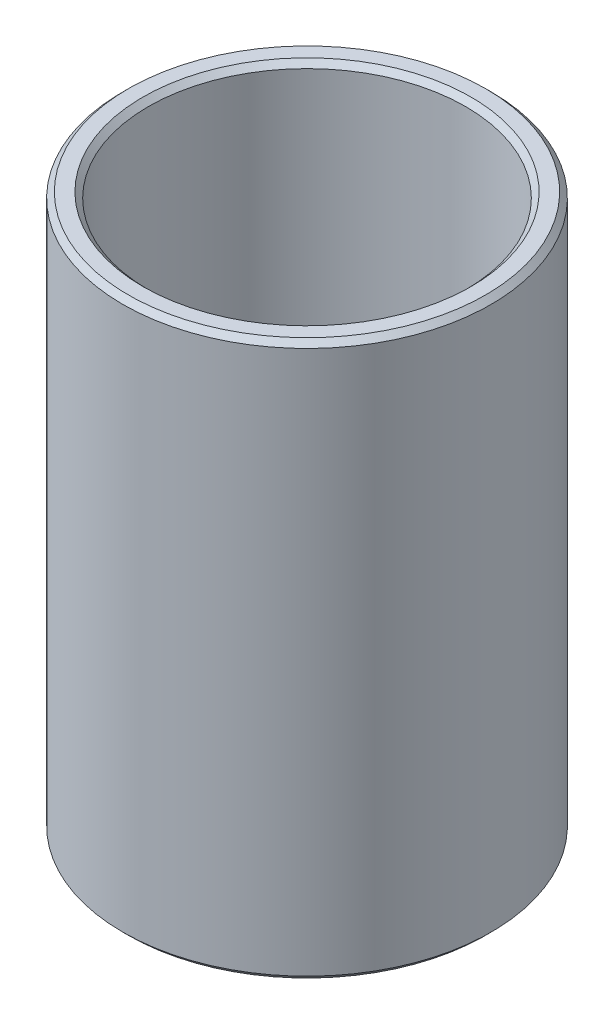
SolidWorks part; units mm, degrees
ref_plane "Front Plane" through (0, 0, 0) normal (0, 0, 1) x (1, 0, 0)
ref_plane "Top Plane" through (0, 0, 0) normal (0, 1, 0) x (1, 0, 0)
ref_plane "Right Plane" through (0, 0, 0) normal (1, 0, 0) x (0, 0, -1)
sketch "Sketch1" plane through (0, 0, 0) normal (0, 1, 0) x (1, 0, 0)
  circle A0 centre (0, 0) radius 50
  dimension "SLEEVE_OD" = 100
extrude "Boss-Extrude1" add sketch "Sketch1" along normal blind 150.5866
sketch "Sketch2" plane through (0, 0, 0) normal (0, 1, 0) x (1, 0, 0)
  circle A0 centre (0, 0) radius 43.0792
  dimension "BORE_D" = 86.1584
extrude "Cut-Extrude1" cut sketch "Sketch2" along normal through all
chamfer "Chamfer1" distance 1.4868 angle 45 4 edges at (0, 150.5866, 43.0792) (0, 0, 43.0792) (0, 0, 50) (0, 150.5866, 50)
